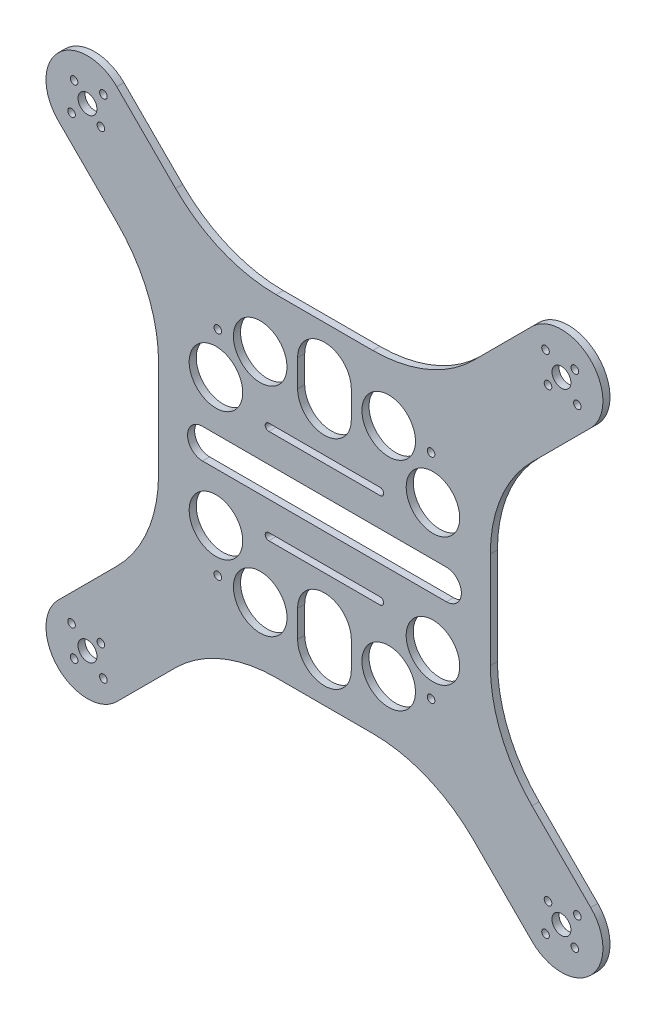
SolidWorks part; units mm, degrees
material "S-Glass Fiber"
ref_plane "Front Plane" through (0, 0, 0) normal (0, 0, 1) x (1, 0, 0)
ref_plane "Top Plane" through (0, 0, 0) normal (0, 1, 0) x (1, 0, 0)
ref_plane "Right Plane" through (0, 0, 0) normal (1, 0, 0) x (0, 0, -1)
sketch "Sketch1" plane through (0, 0, 0) normal (0, 0, 1) x (1, 0, 0)
  line L0 (-112.3744, 87.6256) -> (-87.5736, 62.8249)
  line L1 (-100, 100) -> (100, 100) construction
  line L2 (-100, 100) -> (-100, -100) construction
  line L3 (-100, -100) -> (100, -100) construction
  line L4 (100, 100) -> (100, -100) construction
  line L5 (62.8249, 87.5736) -> (87.6256, 112.3744)
  line L6 (87.5736, 62.8249) -> (112.3744, 87.6256)
  line L7 (-87.6256, 112.3744) -> (-62.8249, 87.5736)
  line L8 (-87.6256, -112.3744) -> (-62.8249, -87.5736)
  line L9 (-112.3744, -87.6256) -> (-87.5736, -62.8249)
  line L10 (87.5736, -62.8249) -> (112.3744, -87.6256)
  line L11 (62.8249, -87.5736) -> (87.6256, -112.3744)
  line L12 (0, 0) -> (-100, 100) construction
  line L13 (-20.3984, 70) -> (20.3984, 70)
  line L14 (-70, 20.3984) -> (-70, -20.3984)
  line L15 (-20.3984, -70) -> (20.3984, -70)
  line L16 (70, 20.3984) -> (70, -20.3984)
  line L17 (0, 0) -> (100, 100) construction
  line L18 (-51.4552, -11.3263) -> (-40.1289, -11.3263) construction
  line L19 (-51.4552, 11.3263) -> (-40.1289, 11.3263) construction
  line L20 (11.3263, 51.4552) -> (11.3263, 40.1289)
  line L21 (-11.3263, 51.4552) -> (-11.3263, 40.1289)
  line L22 (51.4552, 11.3263) -> (40.1289, 11.3263) construction
  line L23 (51.4552, -11.3263) -> (40.1289, -11.3263) construction
  line L24 (11.3263, -51.4552) -> (11.3263, -40.1289)
  line L25 (-11.3263, -51.4552) -> (-11.3263, -40.1289)
  line L26 (-40.1289, -11.3263) -> (40.1289, -11.3263) construction
  line L27 (-40.1289, 11.3263) -> (40.1289, 11.3263) construction
  line L28 (-27.1084, -45.792) -> (23.2474, -45.792) construction
  line L29 (0, -51.4552) -> (0, -40.1289) construction
  line L30 (-77.5344, 0) -> (0, 0) construction
  line L31 (51.4552, 6.3263) -> (40.1289, 6.3263)
  line L32 (-40.1289, 6.3263) -> (40.1289, 6.3263)
  line L33 (-51.4552, 6.3263) -> (-40.1289, 6.3263)
  line L34 (-51.4552, -6.3263) -> (-40.1289, -6.3263)
  line L35 (-40.1289, -6.3263) -> (40.1289, -6.3263)
  line L36 (51.4552, -6.3263) -> (40.1289, -6.3263)
  circle A0 centre (-100, 100) radius 4
  circle A1 centre (100, 100) radius 4
  circle A2 centre (100, -100) radius 4
  circle A3 centre (-100, -100) radius 4
  arc A4 (112.3744, 87.6256) -> (87.6256, 112.3744) centre (100, 100) ccw
  arc A5 (87.6256, -112.3744) -> (112.3744, -87.6256) centre (100, -100) ccw
  arc A6 (-112.3744, -87.6256) -> (-87.6256, -112.3744) centre (-100, -100) ccw
  arc A7 (-87.6256, 112.3744) -> (-112.3744, 87.6256) centre (-100, 100) ccw
  arc A8 (-51.4552, 11.3263) -> (-51.4552, -11.3263) centre (-51.4552, 0) ccw construction
  circle A9 centre (100, 100) radius 75 construction
  circle A10 centre (100, -100) radius 75 construction
  circle A11 centre (-100, -100) radius 75 construction
  circle A12 centre (-100, 100) radius 75 construction
  arc A13 (-70, -20.3984) -> (-87.5736, -62.8249) centre (-130, -20.3984) cw
  arc A14 (-20.3984, -70) -> (-62.8249, -87.5736) centre (-20.3984, -130) ccw
  arc A15 (20.3984, -70) -> (62.8249, -87.5736) centre (20.3984, -130) cw
  arc A16 (70, -20.3984) -> (87.5736, -62.8249) centre (130, -20.3984) ccw
  arc A17 (70, 20.3984) -> (87.5736, 62.8249) centre (130, 20.3984) cw
  arc A18 (20.3984, 70) -> (62.8249, 87.5736) centre (20.3984, 130) ccw
  arc A19 (-20.3984, 70) -> (-62.8249, 87.5736) centre (-20.3984, 130) cw
  arc A20 (-70, 20.3984) -> (-87.5736, 62.8249) centre (-130, 20.3984) ccw
  arc A21 (11.3263, 40.1289) -> (-11.3263, 40.1289) centre (0, 40.1289) cw
  arc A22 (-11.3263, 51.4552) -> (11.3263, 51.4552) centre (0, 51.4552) cw
  circle A23 centre (-27.1084, -45.792) radius 11.2995
  circle A24 centre (27.1084, -45.792) radius 11.2995
  arc A25 (51.4552, -11.3263) -> (51.4552, 11.3263) centre (51.4552, 0) ccw construction
  arc A26 (-11.3263, -40.1289) -> (11.3263, -40.1289) centre (0, -40.1289) cw
  arc A27 (11.3263, -51.4552) -> (-11.3263, -51.4552) centre (0, -51.4552) cw
  circle A28 centre (27.1084, 45.792) radius 11.2995
  circle A29 centre (-27.1084, 45.792) radius 11.2995
  circle A30 centre (-45.792, -27.1084) radius 11.2995
  circle A31 centre (-45.792, 27.1084) radius 11.2995
  circle A32 centre (45.792, -27.1084) radius 11.2995
  circle A33 centre (45.792, 27.1084) radius 11.2995
  arc A34 (51.4552, -6.3263) -> (51.4552, 6.3263) centre (51.4552, 0) ccw
  arc A35 (-51.4552, 6.3263) -> (-51.4552, -6.3263) centre (-51.4552, 0) ccw
  point P0 (0, 0)
  point P20 (0, 0)
  point P31 (0, 0)
  point P39 (0, 0)
  point P41 (0, 0)
  dimension "D1" = 4
  dimension "D6" = 4
  dimension "D2" = 60
  dimension "D3" = 5
extrude "Boss-Extrude2" add sketch "Sketch1" along normal blind 3
sketch "Sketch2" plane through (0, 0, 3) normal (0, 0, 1) x (1, 0, 0)
  line L0 (-100, 100) -> (-100, 92) construction
  line L1 (-100, 100) -> (-93.2825, 93.2825) construction
  line L2 (-100, 100) -> (-106.7175, 93.2825) construction
  line L3 (-100, 100) -> (-93.2825, 106.7175) construction
  line L4 (-100, 100) -> (-106.7175, 106.7175) construction
  line L5 (0, 0) -> (0, -101.3967) construction
  line L6 (0, 0) -> (55.0162, 0) construction
  line L7 (100, 100) -> (106.7175, 106.7175) construction
  line L8 (100, 100) -> (93.2825, 106.7175) construction
  line L9 (100, 100) -> (106.7175, 93.2825) construction
  line L10 (100, 100) -> (93.2825, 93.2825) construction
  line L11 (100, 100) -> (100, 92) construction
  line L12 (-100, -100) -> (-106.7175, -106.7175) construction
  line L13 (-100, -100) -> (-93.2825, -106.7175) construction
  line L14 (-100, -100) -> (-106.7175, -93.2825) construction
  line L15 (-100, -100) -> (-93.2825, -93.2825) construction
  line L16 (-100, -100) -> (-100, -92) construction
  line L17 (100, -100) -> (100, -92) construction
  line L18 (100, -100) -> (93.2825, -93.2825) construction
  line L19 (100, -100) -> (106.7175, -93.2825) construction
  line L20 (100, -100) -> (93.2825, -106.7175) construction
  line L21 (100, -100) -> (106.7175, -106.7175) construction
  circle A0 centre (100, 100) radius 8 construction
  circle A1 centre (100, 100) radius 9.5 construction
  circle A2 centre (106.7175, 93.2825) radius 1.6
  circle A3 centre (105.6569, 105.6569) radius 1.6
  circle A4 centre (-100, 100) radius 9.5 construction
  circle A5 centre (-100, 100) radius 8 construction
  circle A6 centre (93.2825, 106.7175) radius 1.6
  circle A7 centre (94.3431, 94.3431) radius 1.6
  circle A8 centre (-94.3431, 94.3431) radius 1.6
  circle A9 centre (-93.2825, 106.7175) radius 1.6
  circle A10 centre (-105.6569, 105.6569) radius 1.6
  circle A11 centre (-106.7175, 93.2825) radius 1.6
  circle A12 centre (-100, -100) radius 8 construction
  circle A13 centre (-100, -100) radius 9.5 construction
  circle A14 centre (-106.7175, -93.2825) radius 1.6
  circle A15 centre (-105.6569, -105.6569) radius 1.6
  circle A16 centre (-93.2825, -106.7175) radius 1.6
  circle A17 centre (-94.3431, -94.3431) radius 1.6
  circle A18 centre (100, -100) radius 9.5 construction
  circle A19 centre (100, -100) radius 8 construction
  circle A20 centre (94.3431, -94.3431) radius 1.6
  circle A21 centre (93.2825, -106.7175) radius 1.6
  circle A22 centre (105.6569, -105.6569) radius 1.6
  circle A23 centre (106.7175, -93.2825) radius 1.6
  dimension "D7" = 19
  dimension "D8" = 16
  dimension "D13" = 3.2
  dimension "D14" = 3.2
  dimension "D15" = 3.2
  dimension "D16" = 3.2
  dimension "D9" = 45
  dimension "D10" = 90
  dimension "D11" = 90
  dimension "D12" = 90
extrude "Cut-Extrude1" cut sketch "Sketch2" against normal blind 10
sketch "Sketch3" plane through (0, 0, 0) normal (0, 0, -1) x (-1, 0, 0)
  line L0 (0, 0) -> (0, 30.3983) construction
  line L1 (-45, 45) -> (-45, -45) construction
  line L2 (70, 10.671) -> (70, -10.671)
  line L3 (45, -45) -> (-45, -45) construction
  line L4 (45, 45) -> (45, -45) construction
  line L5 (45, 45) -> (-45, 45) construction
  line L6 (0, 0) -> (15.6199, 0) construction
  line L15 (70, 70) -> (-70, 70) construction
  line L16 (70, 70) -> (70, -70) construction
  line L17 (70, -70) -> (-70, -70) construction
  line L18 (-70, 70) -> (-70, -70) construction
  line L19 (70, 70) -> (-70, -70) construction
  line L20 (70, -70) -> (-70, 70) construction
  circle A0 centre (-45, -45) radius 1.6
  circle A1 centre (-100, -100) radius 63.5 construction
  circle A2 centre (-45, 45) radius 1.6
  circle A3 centre (45, 45) radius 1.6
  circle A4 centre (45, -45) radius 1.6
  point P0 (0, 0)
  point P8 (0, 0)
  point P15 (0, 0)
  dimension "D5" = 127
  dimension "D6" = 3.2
  dimension "D2" = 140
  dimension "D3" = 70
  dimension "D4" = 70
  dimension "D1" = 25
extrude "Cut-Extrude2" cut sketch "Sketch3" against normal blind 10 contours A0 | A2 | A3 | A4 region at (45, -45, 0) region at (45, 45, 0) region at (-45, 45, 0) region at (-45, -45, 0)
sketch "Sketch4" plane through (0, 0, 0) normal (0, 0, -1) x (-1, 0, 0)
  line L0 (0, -20) -> (0, 20) construction
  line L1 (70.0013, 20) -> (-70.0013, 20) construction
  line L2 (70.0013, 20) -> (70.0013, -20) construction
  line L3 (70.0013, -20) -> (-70.0013, -20) construction
  line L4 (-70.0013, 20) -> (-70.0013, -20) construction
  line L5 (70.0013, 20) -> (-70.0013, -20) construction
  line L6 (70.0013, -20) -> (-70.0013, 20) construction
  line L8 (25, -18.5) -> (-25, -18.5)
  line L9 (25, -18.5) -> (25, -21.5)
  line L10 (25, -21.5) -> (-25, -21.5)
  line L11 (-25, -18.5) -> (-25, -21.5)
  line L12 (25, -18.5) -> (-25, -21.5) construction
  line L13 (25, -21.5) -> (-25, -18.5) construction
  line L14 (25, 21.5) -> (-25, 21.5)
  line L15 (25, 21.5) -> (25, 18.5)
  line L16 (25, 18.5) -> (-25, 18.5)
  line L17 (-25, 21.5) -> (-25, 18.5)
  line L18 (25, 21.5) -> (-25, 18.5) construction
  line L19 (25, 18.5) -> (-25, 21.5) construction
  arc A0 (-87.5736, -62.8249) -> (-70, -20.3984) centre (-130, -20.3984) ccw construction
  point P0 (0, 0)
  dimension "D1" = 40
  dimension "D2" = 3
  dimension "D3" = 50
  dimension "D4" = 3
  dimension "D5" = 50
extrude "Cut-Extrude3" cut sketch "Sketch4" against normal through all
fillet "Fillet1" radius 1.5 4 edges at (25, 21.5, 1.5) (25, 18.5, 1.5) (-25, 18.5, 1.5) (-25, 21.5, 1.5)
fillet "Fillet2" radius 1.5 4 edges at (-25, -21.5, 1.5) (-25, -18.5, 1.5) (25, -21.5, 1.5) (25, -18.5, 1.5)
